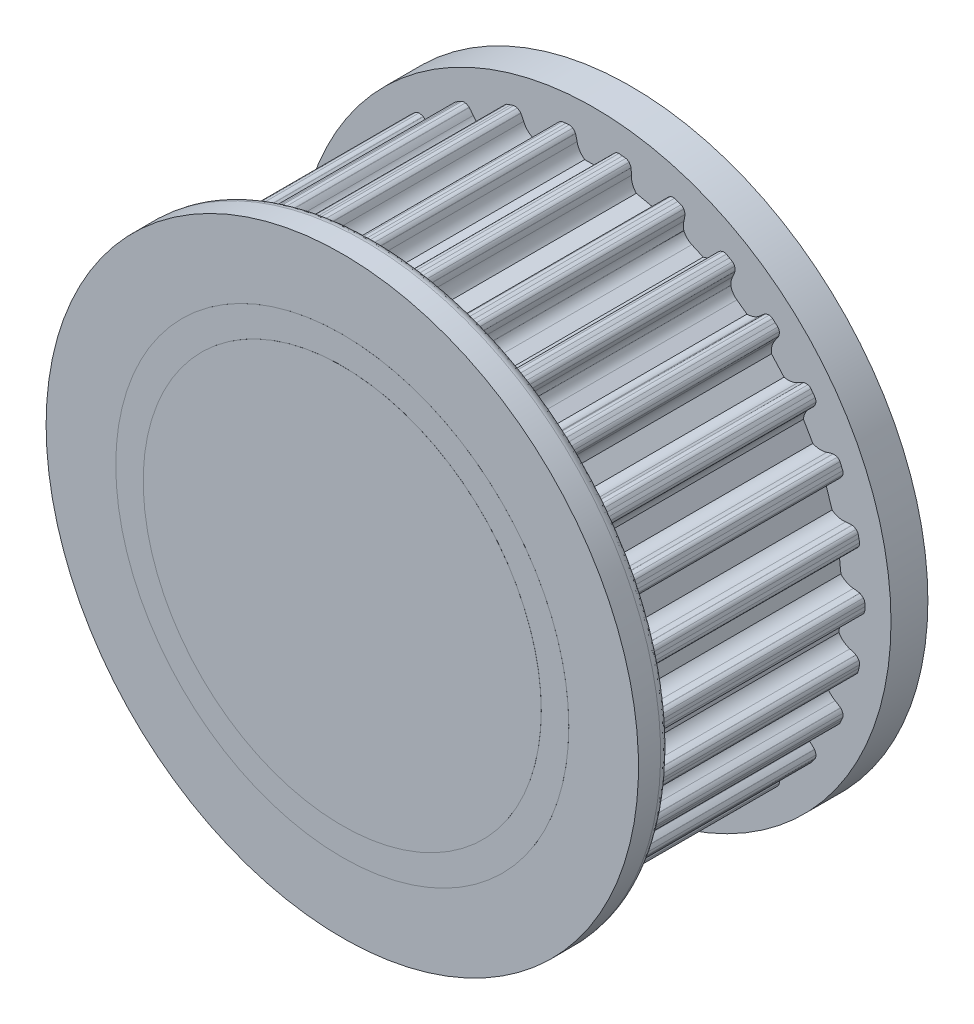
SolidWorks part; units mm, degrees
ref_plane "Front Plane" through (0, 0, 0) normal (0, 0, 1) x (1, 0, 0)
ref_plane "Top Plane" through (0, 0, 0) normal (0, 1, 0) x (1, 0, 0)
ref_plane "Right Plane" through (0, 0, 0) normal (1, 0, 0) x (0, 0, -1)
sketch "Sketch1" plane through (0, 0, 0) normal (0, 1, 0) x (1, 0, 0)
  line L0 (23.3317, 12.425) -> (0, 12.425)
  line L1 (0, 12.425) -> (0, 9.25)
  line L2 (0, 9.25) -> (23.3, 9.25)
  line L3 (23.3, 9.25) -> (25.5635, 9.25)
  line L4 (25.5635, 9.25) -> (25.5635, 12.425)
  line L5 (25.5635, 12.425) -> (23.3317, 12.425)
  line L6 (0, 11) -> (0, 9.25) construction
revolve "Revolve1" add sketch "Sketch1" angle 360 about L6 reverse direction yes
sketch "Sketch2" plane through (0, 0, -9.25) normal (0, 0, 1) x (1, 0, 0)
  line L0 (-22.221, 5.5321) -> (-22.1985, 5.5355)
  line L1 (-20.4892, 5.807) -> (-19.9894, 7.3453)
  line L2 (-21.2127, 8.5696) -> (-21.2288, 8.5856)
  line L3 (-20.5852, 10.0312) -> (-20.5625, 10.0299)
  line L4 (-18.8341, 9.9401) -> (-18.0254, 11.3408)
  line L5 (-18.9674, 12.7927) -> (-18.9799, 12.8117)
  line L6 (-18.0497, 14.0919) -> (-18.0278, 14.0859)
  line L7 (-16.3559, 13.6387) -> (-15.2736, 14.8406)
  line L8 (-15.8932, 16.4567) -> (-15.9015, 16.4779)
  line L9 (-14.7254, 17.5368) -> (-14.7053, 17.5263)
  line L10 (-13.1628, 16.7412) -> (-11.8543, 17.6919)
  line L11 (-12.1243, 19.4015) -> (-12.128, 19.4239)
  line L12 (-10.7575, 20.2151) -> (-10.74, 20.2007)
  line L13 (-9.3945, 19.1121) -> (-7.9169, 19.7699)
  line L14 (-7.8256, 21.4983) -> (-7.8246, 21.521)
  line L15 (-6.3195, 22.01) -> (-6.3053, 21.9922)
  line L16 (-5.2156, 20.6476) -> (-3.6335, 20.9839)
  line L17 (-3.1848, 22.6555) -> (-3.1791, 22.6775)
  line L18 (-1.6053, 22.8429) -> (-1.5951, 22.8226)
  line L19 (-0.8087, 21.2808) -> (0.8087, 21.2808)
  line L20 (1.5951, 22.8226) -> (1.6053, 22.8429)
  line L21 (3.1791, 22.6775) -> (3.1848, 22.6555)
  line L22 (3.6335, 20.9839) -> (5.2156, 20.6476)
  line L23 (6.3053, 21.9922) -> (6.3195, 22.01)
  line L24 (7.8246, 21.521) -> (7.8256, 21.4983)
  line L25 (7.7272, 20.2583) -> (7.9401, 19.7596)
  line L26 (7.9401, 19.7596) -> (9.3945, 19.1121)
  line L27 (10.74, 20.2007) -> (10.7575, 20.2151)
  line L28 (12.128, 19.4239) -> (12.1243, 19.4015)
  line L29 (11.7703, 18.209) -> (11.8749, 17.677)
  line L30 (11.8749, 17.677) -> (13.1628, 16.7412)
  line L31 (14.7053, 17.5263) -> (14.7254, 17.5368)
  line L32 (15.9015, 16.4779) -> (15.8932, 16.4567)
  line L33 (15.2736, 14.8406) -> (16.3559, 13.6387)
  line L34 (18.0278, 14.0859) -> (18.0497, 14.0919)
  line L35 (18.9799, 12.8117) -> (18.9674, 12.7927)
  line L36 (18.0254, 11.3408) -> (18.8341, 9.9401)
  line L37 (20.5625, 10.0299) -> (20.5852, 10.0312)
  line L38 (21.2288, 8.5856) -> (21.2127, 8.5696)
  line L39 (19.9894, 7.3453) -> (20.4892, 5.807)
  line L40 (22.1985, 5.5355) -> (22.221, 5.5321)
  line L41 (22.55, 3.9842) -> (22.5308, 3.972)
  line L42 (21.0797, 3.0287) -> (21.2488, 1.4202)
  line L43 (22.8643, 0.7992) -> (22.8856, 0.7912)
  line L44 (22.8856, -0.7912) -> (22.8643, -0.7992)
  line L45 (21.2488, -1.4202) -> (21.0797, -3.0287)
  line L46 (22.5308, -3.972) -> (22.55, -3.9842)
  line L47 (22.221, -5.5321) -> (22.1985, -5.5355)
  line L48 (20.4892, -5.807) -> (19.9894, -7.3453)
  line L49 (21.2127, -8.5696) -> (21.2288, -8.5856)
  line L50 (20.5852, -10.0312) -> (20.5625, -10.0299)
  line L51 (18.8341, -9.9401) -> (18.0254, -11.3408)
  line L52 (18.9674, -12.7927) -> (18.9799, -12.8117)
  line L53 (18.0497, -14.0919) -> (18.0278, -14.0859)
  line L54 (16.3559, -13.6387) -> (15.2736, -14.8406)
  line L55 (15.8932, -16.4567) -> (15.9015, -16.4779)
  line L56 (14.7254, -17.5368) -> (14.7053, -17.5263)
  line L57 (13.1628, -16.7412) -> (11.8749, -17.677)
  line L58 (11.8749, -17.677) -> (11.7703, -18.209)
  line L59 (12.1243, -19.4015) -> (12.128, -19.4239)
  line L60 (10.7575, -20.2151) -> (10.74, -20.2007)
  line L61 (9.3945, -19.1121) -> (7.9401, -19.7596)
  line L62 (7.9401, -19.7596) -> (7.7272, -20.2583)
  line L63 (7.8256, -21.4983) -> (7.8246, -21.521)
  line L64 (6.3195, -22.01) -> (6.3053, -21.9922)
  line L65 (5.2156, -20.6476) -> (3.6335, -20.9839)
  line L66 (3.1848, -22.6555) -> (3.1791, -22.6775)
  line L67 (1.6053, -22.8429) -> (1.5951, -22.8226)
  line L68 (0.8087, -21.2808) -> (-0.8087, -21.2808)
  line L69 (-1.5951, -22.8226) -> (-1.6053, -22.8429)
  line L70 (-3.1791, -22.6775) -> (-3.1848, -22.6555)
  line L71 (-3.6335, -20.9839) -> (-5.2156, -20.6476)
  line L72 (-6.3053, -21.9922) -> (-6.3195, -22.01)
  line L73 (-7.8246, -21.521) -> (-7.8256, -21.4983)
  line L74 (-7.9169, -19.7699) -> (-9.3945, -19.1121)
  line L75 (-10.74, -20.2007) -> (-10.7575, -20.2151)
  line L76 (-12.128, -19.4239) -> (-12.1243, -19.4015)
  line L77 (-11.8543, -17.6919) -> (-13.1628, -16.7412)
  line L78 (-14.7053, -17.5263) -> (-14.7254, -17.5368)
  line L79 (-15.9015, -16.4779) -> (-15.8932, -16.4567)
  line L80 (-15.2736, -14.8406) -> (-16.3559, -13.6387)
  line L81 (-18.0278, -14.0859) -> (-18.0497, -14.0919)
  line L82 (-18.9799, -12.8117) -> (-18.9674, -12.7927)
  line L83 (-18.0254, -11.3408) -> (-18.8341, -9.9401)
  line L84 (-20.5625, -10.0299) -> (-20.5852, -10.0312)
  line L85 (-21.2288, -8.5856) -> (-21.2127, -8.5696)
  line L86 (-19.9894, -7.3453) -> (-20.4892, -5.807)
  line L87 (-22.1985, -5.5355) -> (-22.221, -5.5321)
  line L88 (-22.55, -3.9842) -> (-22.5308, -3.972)
  line L89 (-21.0797, -3.0287) -> (-21.2488, -1.4202)
  line L90 (-22.8643, -0.7992) -> (-22.8856, -0.7912)
  line L91 (-22.8856, 0.7912) -> (-22.8643, 0.7992)
  line L92 (-21.2488, 1.4202) -> (-21.0797, 3.0287)
  line L93 (-22.5308, 3.972) -> (-22.55, 3.9842)
  arc A0 (-22.8557, 4.5501) -> (-22.7941, 4.845) centre (-18.765, 3.8489) cw
  arc A1 (-22.7941, 4.845) -> (-22.7305, 5.1395) centre (-18.7082, 4.1162) cw
  arc A2 (-22.7305, 5.1395) -> (-22.5533, 5.3971) centre (-22.2151, 4.9748) cw
  arc A3 (-22.5533, 5.3971) -> (-22.221, 5.5321) centre (-22.0388, 4.6076) cw
  arc A4 (-22.1985, 5.5355) -> (-21.6552, 5.4979) centre (-22.2209, 1.2735) cw
  arc A5 (-21.6552, 5.4979) -> (-20.4892, 5.807) centre (-21.4632, 7.1274) ccw
  arc A6 (-19.9894, 7.3453) -> (-20.751, 8.2807) centre (-21.5535, 6.8495) ccw
  arc A7 (-20.751, 8.2807) -> (-21.2127, 8.5696) centre (-18.7256, 12.0308) cw
  arc A8 (-21.2288, 8.5856) -> (-21.4183, 8.8902) centre (-20.538, 9.2265) cw
  arc A9 (-21.4183, 8.8902) -> (-21.4102, 9.2027) centre (-20.8965, 9.0331) cw
  arc A10 (-21.4102, 9.2027) -> (-21.2886, 9.4783) centre (-17.5547, 7.6663) cw
  arc A11 (-21.2886, 9.4783) -> (-21.1652, 9.7531) centre (-17.4436, 7.916) cw
  arc A12 (-21.1652, 9.7531) -> (-20.9383, 9.9682) centre (-20.6954, 9.4848) cw
  arc A13 (-20.9383, 9.9682) -> (-20.5852, 10.0312) centre (-20.5992, 9.089) cw
  arc A14 (-20.5625, 10.0299) -> (-20.0389, 9.8801) centre (-21.4705, 5.8657) cw
  arc A15 (-20.0389, 9.8801) -> (-18.8341, 9.9401) centre (-19.5123, 11.4341) ccw
  arc A16 (-18.0254, 11.3408) -> (-18.5759, 12.4142) centre (-19.6584, 11.1811) ccw
  arc A17 (-18.5759, 12.4142) -> (-18.9674, 12.7927) centre (-15.8151, 15.6612) cw
  arc A18 (-18.9799, 12.8117) -> (-19.1019, 13.149) centre (-18.1709, 13.295) cw
  arc A19 (-19.1019, 13.149) -> (-19.029, 13.453) centre (-18.5618, 13.1803) cw
  arc A20 (-19.029, 13.453) -> (-18.8528, 13.6973) centre (-15.5772, 11.1486) cw
  arc A21 (-18.8528, 13.6973) -> (-18.6749, 13.9405) centre (-15.4166, 11.3697) cw
  arc A22 (-18.6749, 13.9405) -> (-18.4083, 14.1037) centre (-18.2711, 13.5804) cw
  arc A23 (-18.4083, 14.1037) -> (-18.0497, 14.0919) centre (-18.2594, 13.1732) cw
  arc A24 (-18.0278, 14.0859) -> (-17.5468, 13.8305) centre (-19.7818, 10.2014) cw
  arc A25 (-17.5468, 13.8305) -> (-16.3559, 13.6387) centre (-16.7086, 15.2411) ccw
  arc A26 (-15.2736, 14.8406) -> (-15.5889, 16.005) centre (-16.9042, 15.024) ccw
  arc A27 (-15.5889, 16.005) -> (-15.8932, 16.4567) centre (-12.2133, 18.6071) cw
  arc A28 (-15.9015, 16.4779) -> (-15.9507, 16.8332) centre (-15.0097, 16.7824) cw
  arc A29 (-15.9507, 16.8332) -> (-15.8162, 17.1154) centre (-15.4158, 16.7515) cw
  arc A30 (-15.8162, 17.1154) -> (-15.593, 17.3177) centre (-12.9189, 14.1437) cw
  arc A31 (-15.593, 17.3177) -> (-15.3684, 17.5186) centre (-12.7158, 14.3265) cw
  arc A32 (-15.3684, 17.5186) -> (-15.0737, 17.6228) centre (-15.0483, 17.0824) cw
  arc A33 (-15.0737, 17.6228) -> (-14.7254, 17.5368) centre (-15.1215, 16.6817) cw
  arc A34 (-14.7053, 17.5263) -> (-14.2879, 17.1765) centre (-17.2285, 14.0914) cw
  arc A35 (-14.2879, 17.1765) -> (-13.1628, 16.7412) centre (-13.1747, 18.382) ccw
  arc A36 (-11.8543, 17.6919) -> (-11.9206, 18.8964) centre (-13.4111, 18.2102) ccw
  arc A37 (-11.9206, 18.8964) -> (-12.1243, 19.4015) centre (-8.0778, 20.7398) cw
  arc A38 (-12.128, 19.4239) -> (-12.1023, 19.7817) centre (-11.1924, 19.5363) cw
  arc A39 (-12.1023, 19.7817) -> (-11.9121, 20.0298) centre (-11.5961, 19.5906) cw
  arc A40 (-11.9121, 20.0298) -> (-11.6517, 20.1813) centre (-9.6959, 16.5206) cw
  arc A41 (-11.6517, 20.1813) -> (-11.3902, 20.331) centre (-9.4593, 16.6572) cw
  arc A42 (-11.3902, 20.331) -> (-11.0803, 20.3717) centre (-11.1678, 19.8378) cw
  arc A43 (-11.0803, 20.3717) -> (-10.7575, 20.2151) centre (-11.3228, 19.4611) cw
  arc A44 (-10.74, 20.2007) -> (-10.4045, 19.7718) centre (-13.9223, 17.3655) cw
  arc A45 (-10.4045, 19.7718) -> (-9.3945, 19.1121) centre (-9.065, 20.7195) ccw
  arc A46 (-7.9169, 19.7699) -> (-7.7313, 20.9619) centre (-9.3319, 20.6006) ccw
  arc A47 (-7.7313, 20.9619) -> (-7.8256, 21.4983) centre (-3.5892, 21.966) cw
  arc A48 (-7.8246, 21.521) -> (-7.725, 21.8656) centre (-6.886, 21.4365) cw
  arc A49 (-7.725, 21.8656) -> (-7.4873, 22.0687) centre (-7.2696, 21.5734) cw
  arc A50 (-7.4873, 22.0687) -> (-7.2011, 22.1628) centre (-6.0492, 18.1755) cw
  arc A51 (-7.2011, 22.1628) -> (-6.9143, 22.2549) centre (-5.7893, 18.2599) cw
  arc A52 (-6.9143, 22.2549) -> (-6.6026, 22.2303) centre (-6.7993, 21.7262) cw
  arc A53 (-6.6026, 22.2303) -> (-6.3195, 22.01) centre (-7.0291, 21.39) cw
  arc A54 (-6.3053, 21.9922) -> (-6.0663, 21.5029) centre (-10.0076, 19.8806) cw
  arc A55 (-6.0663, 21.5029) -> (-5.2156, 20.6476) centre (-4.5591, 22.1514) ccw
  arc A56 (-3.6335, 20.9839) -> (-3.2042, 22.1113) centre (-4.8449, 22.0907) ccw
  arc A57 (-3.2042, 22.1113) -> (-3.1848, 22.6555) centre (1.0562, 22.2323) cw
  arc A58 (-3.1791, 22.6775) -> (-3.0101, 22.9939) centre (-2.2786, 22.3997) cw
  arc A59 (-3.0101, 22.9939) -> (-2.7354, 23.1432) centre (-2.6254, 22.6134) cw
  arc A60 (-2.7354, 23.1432) -> (-2.4359, 23.1757) centre (-2.1382, 19.036) cw
  arc A61 (-2.4359, 23.1757) -> (-2.1361, 23.2061) centre (-1.8664, 19.0646) cw
  arc A62 (-2.1361, 23.2061) -> (-1.8364, 23.1172) centre (-2.1336, 22.6651) cw
  arc A63 (-1.8364, 23.1172) -> (-1.6053, 22.8429) centre (-2.4283, 22.384) cw
  arc A64 (-1.5951, 22.8226) -> (-1.463, 22.2943) centre (-5.6555, 21.5268) cw
  arc A65 (-1.463, 22.2943) -> (-0.8087, 21.2808) centre (0.1461, 22.6152) ccw
  arc A66 (0.8087, 21.2808) -> (1.463, 22.2943) centre (-0.1461, 22.6152) ccw
  arc A67 (1.463, 22.2943) -> (1.5951, 22.8226) centre (5.6555, 21.5268) cw
  arc A68 (1.6053, 22.8429) -> (1.8364, 23.1172) centre (2.4283, 22.384) cw
  arc A69 (1.8364, 23.1172) -> (2.1361, 23.2061) centre (2.1336, 22.6651) cw
  arc A70 (2.1361, 23.2061) -> (2.4359, 23.1757) centre (1.8664, 19.0646) cw
  arc A71 (2.4359, 23.1757) -> (2.7354, 23.1432) centre (2.1382, 19.036) cw
  arc A72 (2.7354, 23.1432) -> (3.0101, 22.9939) centre (2.6254, 22.6134) cw
  arc A73 (3.0101, 22.9939) -> (3.1791, 22.6775) centre (2.2786, 22.3997) cw
  arc A74 (3.1848, 22.6555) -> (3.2042, 22.1113) centre (-1.0562, 22.2323) cw
  arc A75 (3.2042, 22.1113) -> (3.6335, 20.9839) centre (4.8449, 22.0907) ccw
  arc A76 (5.2156, 20.6476) -> (6.0663, 21.5029) centre (4.5591, 22.1514) ccw
  arc A77 (6.0663, 21.5029) -> (6.3053, 21.9922) centre (10.0076, 19.8806) cw
  arc A78 (6.3195, 22.01) -> (6.6026, 22.2303) centre (7.0291, 21.39) cw
  arc A79 (6.6026, 22.2303) -> (6.9143, 22.2549) centre (6.7993, 21.7262) cw
  arc A80 (6.9143, 22.2549) -> (7.2011, 22.1628) centre (5.7893, 18.2599) cw
  arc A81 (7.2011, 22.1628) -> (7.4873, 22.0687) centre (6.0492, 18.1755) cw
  arc A82 (7.4873, 22.0687) -> (7.725, 21.8656) centre (7.2696, 21.5734) cw
  arc A83 (7.725, 21.8656) -> (7.8246, 21.521) centre (6.886, 21.4365) cw
  arc A84 (7.8256, 21.4983) -> (7.7313, 20.9619) centre (3.5892, 21.966) cw
  arc A85 (7.7313, 20.9619) -> (7.7272, 20.2583) centre (9.3319, 20.6006) ccw
  arc A86 (9.3945, 19.1121) -> (10.4045, 19.7718) centre (9.065, 20.7195) ccw
  arc A87 (10.4045, 19.7718) -> (10.74, 20.2007) centre (13.9223, 17.3655) cw
  arc A88 (10.7575, 20.2151) -> (11.0803, 20.3717) centre (11.3228, 19.4611) cw
  arc A89 (11.0803, 20.3717) -> (11.3902, 20.331) centre (11.1678, 19.8378) cw
  arc A90 (11.3902, 20.331) -> (11.6517, 20.1813) centre (9.4593, 16.6572) cw
  arc A91 (11.6517, 20.1813) -> (11.9121, 20.0298) centre (9.6959, 16.5206) cw
  arc A92 (11.9121, 20.0298) -> (12.1023, 19.7817) centre (11.5961, 19.5906) cw
  arc A93 (12.1023, 19.7817) -> (12.128, 19.4239) centre (11.1924, 19.5363) cw
  arc A94 (12.1243, 19.4015) -> (11.9206, 18.8964) centre (8.0778, 20.7398) cw
  arc A95 (11.9206, 18.8964) -> (11.7703, 18.209) centre (13.4111, 18.2102) ccw
  arc A96 (13.1628, 16.7412) -> (14.2879, 17.1765) centre (13.1747, 18.382) ccw
  arc A97 (14.2879, 17.1765) -> (14.7053, 17.5263) centre (17.2285, 14.0914) cw
  arc A98 (14.7254, 17.5368) -> (15.0737, 17.6228) centre (15.1215, 16.6817) cw
  arc A99 (15.0737, 17.6228) -> (15.3684, 17.5186) centre (15.0483, 17.0824) cw
  arc A100 (15.3684, 17.5186) -> (15.593, 17.3177) centre (12.7158, 14.3265) cw
  arc A101 (15.593, 17.3177) -> (15.8162, 17.1154) centre (12.9189, 14.1437) cw
  arc A102 (15.8162, 17.1154) -> (15.9507, 16.8332) centre (15.4158, 16.7515) cw
  arc A103 (15.9507, 16.8332) -> (15.9015, 16.4779) centre (15.0097, 16.7824) cw
  arc A104 (15.8932, 16.4567) -> (15.5889, 16.005) centre (12.2133, 18.6071) cw
  arc A105 (15.5889, 16.005) -> (15.2736, 14.8406) centre (16.9042, 15.024) ccw
  arc A106 (16.3559, 13.6387) -> (17.5468, 13.8305) centre (16.7086, 15.2411) ccw
  arc A107 (17.5468, 13.8305) -> (18.0278, 14.0859) centre (19.7818, 10.2014) cw
  arc A108 (18.0497, 14.0919) -> (18.4083, 14.1037) centre (18.2594, 13.1732) cw
  arc A109 (18.4083, 14.1037) -> (18.6749, 13.9405) centre (18.2711, 13.5804) cw
  arc A110 (18.6749, 13.9405) -> (18.8528, 13.6973) centre (15.4166, 11.3697) cw
  arc A111 (18.8528, 13.6973) -> (19.029, 13.453) centre (15.5772, 11.1486) cw
  arc A112 (19.029, 13.453) -> (19.1019, 13.149) centre (18.5618, 13.1803) cw
  arc A113 (19.1019, 13.149) -> (18.9799, 12.8117) centre (18.1709, 13.295) cw
  arc A114 (18.9674, 12.7927) -> (18.5759, 12.4142) centre (15.8151, 15.6612) cw
  arc A115 (18.5759, 12.4142) -> (18.0254, 11.3408) centre (19.6584, 11.1811) ccw
  arc A116 (18.8341, 9.9401) -> (20.0389, 9.8801) centre (19.5123, 11.4341) ccw
  arc A117 (20.0389, 9.8801) -> (20.5625, 10.0299) centre (21.4705, 5.8657) cw
  arc A118 (20.5852, 10.0312) -> (20.9383, 9.9682) centre (20.5992, 9.089) cw
  arc A119 (20.9383, 9.9682) -> (21.1652, 9.7531) centre (20.6954, 9.4848) cw
  arc A120 (21.1652, 9.7531) -> (21.2886, 9.4783) centre (17.4436, 7.916) cw
  arc A121 (21.2886, 9.4783) -> (21.4102, 9.2027) centre (17.5547, 7.6663) cw
  arc A122 (21.4102, 9.2027) -> (21.4183, 8.8902) centre (20.8965, 9.0331) cw
  arc A123 (21.4183, 8.8902) -> (21.2288, 8.5856) centre (20.538, 9.2265) cw
  arc A124 (21.2127, 8.5696) -> (20.751, 8.2807) centre (18.7256, 12.0308) cw
  arc A125 (20.751, 8.2807) -> (19.9894, 7.3453) centre (21.5535, 6.8495) ccw
  arc A126 (20.4892, 5.807) -> (21.6552, 5.4979) centre (21.4632, 7.1274) ccw
  arc A127 (21.6552, 5.4979) -> (22.1985, 5.5355) centre (22.2209, 1.2735) cw
  arc A128 (22.221, 5.5321) -> (22.5533, 5.3971) centre (22.0388, 4.6076) cw
  arc A129 (22.5533, 5.3971) -> (22.7305, 5.1395) centre (22.2151, 4.9748) cw
  arc A130 (22.7305, 5.1395) -> (22.7941, 4.845) centre (18.7082, 4.1162) cw
  arc A131 (22.7941, 4.845) -> (22.8557, 4.5501) centre (18.765, 3.8489) cw
  arc A132 (22.8557, 4.5501) -> (22.7986, 4.2428) centre (22.3179, 4.491) cw
  arc A133 (22.7986, 4.2428) -> (22.55, 3.9842) centre (22.0075, 4.7548) cw
  arc A134 (22.5308, 3.972) -> (22.0192, 3.7854) centre (20.8178, 7.8746) cw
  arc A135 (22.0192, 3.7854) -> (21.0797, 3.0287) centre (22.5066, 2.2186) ccw
  arc A136 (21.2488, 1.4202) -> (22.3251, 0.8754) centre (22.4761, 2.5092) ccw
  arc A137 (22.3251, 0.8754) -> (22.8643, 0.7992) centre (22.0001, -3.3743) cw
  arc A138 (22.8856, 0.7912) -> (23.1826, 0.59) centre (22.5152, -0.0752) cw
  arc A139 (23.1826, 0.59) -> (23.3023, 0.3013) centre (22.764, 0.2473) cw
  arc A140 (23.3023, 0.3013) -> (23.3033, 0) centre (19.1552, 0.1366) cw
  arc A141 (23.3033, 0) -> (23.3023, -0.3013) centre (19.1552, -0.1366) cw
  arc A142 (23.3023, -0.3013) -> (23.1826, -0.59) centre (22.764, -0.2473) cw
  arc A143 (23.1826, -0.59) -> (22.8856, -0.7912) centre (22.5152, 0.0752) cw
  arc A144 (22.8643, -0.7992) -> (22.3251, -0.8754) centre (22.0001, 3.3743) cw
  arc A145 (22.3251, -0.8754) -> (21.2488, -1.4202) centre (22.4761, -2.5092) ccw
  arc A146 (21.0797, -3.0287) -> (22.0192, -3.7854) centre (22.5066, -2.2186) ccw
  arc A147 (22.0192, -3.7854) -> (22.5308, -3.972) centre (20.8178, -7.8746) cw
  arc A148 (22.55, -3.9842) -> (22.7986, -4.2428) centre (22.0075, -4.7548) cw
  arc A149 (22.7986, -4.2428) -> (22.8557, -4.5501) centre (22.3179, -4.491) cw
  arc A150 (22.8557, -4.5501) -> (22.7941, -4.845) centre (18.765, -3.8489) cw
  arc A151 (22.7941, -4.845) -> (22.7305, -5.1395) centre (18.7082, -4.1162) cw
  arc A152 (22.7305, -5.1395) -> (22.5533, -5.3971) centre (22.2151, -4.9748) cw
  arc A153 (22.5533, -5.3971) -> (22.221, -5.5321) centre (22.0388, -4.6076) cw
  arc A154 (22.1985, -5.5355) -> (21.6552, -5.4979) centre (22.2209, -1.2735) cw
  arc A155 (21.6552, -5.4979) -> (20.4892, -5.807) centre (21.4632, -7.1274) ccw
  arc A156 (19.9894, -7.3453) -> (20.751, -8.2807) centre (21.5535, -6.8495) ccw
  arc A157 (20.751, -8.2807) -> (21.2127, -8.5696) centre (18.7256, -12.0308) cw
  arc A158 (21.2288, -8.5856) -> (21.4183, -8.8902) centre (20.538, -9.2265) cw
  arc A159 (21.4183, -8.8902) -> (21.4102, -9.2027) centre (20.8965, -9.0331) cw
  arc A160 (21.4102, -9.2027) -> (21.2886, -9.4783) centre (17.5547, -7.6663) cw
  arc A161 (21.2886, -9.4783) -> (21.1652, -9.7531) centre (17.4436, -7.916) cw
  arc A162 (21.1652, -9.7531) -> (20.9383, -9.9682) centre (20.6954, -9.4848) cw
  arc A163 (20.9383, -9.9682) -> (20.5852, -10.0312) centre (20.5992, -9.089) cw
  arc A164 (20.5625, -10.0299) -> (20.0389, -9.8801) centre (21.4705, -5.8657) cw
  arc A165 (20.0389, -9.8801) -> (18.8341, -9.9401) centre (19.5123, -11.4341) ccw
  arc A166 (18.0254, -11.3408) -> (18.5759, -12.4142) centre (19.6584, -11.1811) ccw
  arc A167 (18.5759, -12.4142) -> (18.9674, -12.7927) centre (15.8151, -15.6612) cw
  arc A168 (18.9799, -12.8117) -> (19.1019, -13.149) centre (18.1709, -13.295) cw
  arc A169 (19.1019, -13.149) -> (19.029, -13.453) centre (18.5618, -13.1803) cw
  arc A170 (19.029, -13.453) -> (18.8528, -13.6973) centre (15.5772, -11.1486) cw
  arc A171 (18.8528, -13.6973) -> (18.6749, -13.9405) centre (15.4166, -11.3697) cw
  arc A172 (18.6749, -13.9405) -> (18.4083, -14.1037) centre (18.2711, -13.5804) cw
  arc A173 (18.4083, -14.1037) -> (18.0497, -14.0919) centre (18.2594, -13.1732) cw
  arc A174 (18.0278, -14.0859) -> (17.5468, -13.8305) centre (19.7818, -10.2014) cw
  arc A175 (17.5468, -13.8305) -> (16.3559, -13.6387) centre (16.7086, -15.2411) ccw
  arc A176 (15.2736, -14.8406) -> (15.5889, -16.005) centre (16.9042, -15.024) ccw
  arc A177 (15.5889, -16.005) -> (15.8932, -16.4567) centre (12.2133, -18.6071) cw
  arc A178 (15.9015, -16.4779) -> (15.9507, -16.8332) centre (15.0097, -16.7824) cw
  arc A179 (15.9507, -16.8332) -> (15.8162, -17.1154) centre (15.4158, -16.7515) cw
  arc A180 (15.8162, -17.1154) -> (15.593, -17.3177) centre (12.9189, -14.1437) cw
  arc A181 (15.593, -17.3177) -> (15.3684, -17.5186) centre (12.7158, -14.3265) cw
  arc A182 (15.3684, -17.5186) -> (15.0737, -17.6228) centre (15.0483, -17.0824) cw
  arc A183 (15.0737, -17.6228) -> (14.7254, -17.5368) centre (15.1215, -16.6817) cw
  arc A184 (14.7053, -17.5263) -> (14.2879, -17.1765) centre (17.2285, -14.0914) cw
  arc A185 (14.2879, -17.1765) -> (13.1628, -16.7412) centre (13.1747, -18.382) ccw
  arc A186 (11.7703, -18.209) -> (11.9206, -18.8964) centre (13.4111, -18.2102) ccw
  arc A187 (11.9206, -18.8964) -> (12.1243, -19.4015) centre (8.0778, -20.7398) cw
  arc A188 (12.128, -19.4239) -> (12.1023, -19.7817) centre (11.1924, -19.5363) cw
  arc A189 (12.1023, -19.7817) -> (11.9121, -20.0298) centre (11.5961, -19.5906) cw
  arc A190 (11.9121, -20.0298) -> (11.6517, -20.1813) centre (9.6959, -16.5206) cw
  arc A191 (11.6517, -20.1813) -> (11.3902, -20.331) centre (9.4593, -16.6572) cw
  arc A192 (11.3902, -20.331) -> (11.0803, -20.3717) centre (11.1678, -19.8378) cw
  arc A193 (11.0803, -20.3717) -> (10.7575, -20.2151) centre (11.3228, -19.4611) cw
  arc A194 (10.74, -20.2007) -> (10.4045, -19.7718) centre (13.9223, -17.3655) cw
  arc A195 (10.4045, -19.7718) -> (9.3945, -19.1121) centre (9.065, -20.7195) ccw
  arc A196 (7.7272, -20.2583) -> (7.7313, -20.9619) centre (9.3319, -20.6006) ccw
  arc A197 (7.7313, -20.9619) -> (7.8256, -21.4983) centre (3.5892, -21.966) cw
  arc A198 (7.8246, -21.521) -> (7.725, -21.8656) centre (6.886, -21.4365) cw
  arc A199 (7.725, -21.8656) -> (7.4873, -22.0687) centre (7.2696, -21.5734) cw
  arc A200 (7.4873, -22.0687) -> (7.2011, -22.1628) centre (6.0492, -18.1755) cw
  arc A201 (7.2011, -22.1628) -> (6.9143, -22.2549) centre (5.7893, -18.2599) cw
  arc A202 (6.9143, -22.2549) -> (6.6026, -22.2303) centre (6.7993, -21.7262) cw
  arc A203 (6.6026, -22.2303) -> (6.3195, -22.01) centre (7.0291, -21.39) cw
  arc A204 (6.3053, -21.9922) -> (6.0663, -21.5029) centre (10.0076, -19.8806) cw
  arc A205 (6.0663, -21.5029) -> (5.2156, -20.6476) centre (4.5591, -22.1514) ccw
  arc A206 (3.6335, -20.9839) -> (3.2042, -22.1113) centre (4.8449, -22.0907) ccw
  arc A207 (3.2042, -22.1113) -> (3.1848, -22.6555) centre (-1.0562, -22.2323) cw
  arc A208 (3.1791, -22.6775) -> (3.0101, -22.9939) centre (2.2786, -22.3997) cw
  arc A209 (3.0101, -22.9939) -> (2.7354, -23.1432) centre (2.6254, -22.6134) cw
  arc A210 (2.7354, -23.1432) -> (2.4359, -23.1757) centre (2.1382, -19.036) cw
  arc A211 (2.4359, -23.1757) -> (2.1361, -23.2061) centre (1.8664, -19.0646) cw
  arc A212 (2.1361, -23.2061) -> (1.8364, -23.1172) centre (2.1336, -22.6651) cw
  arc A213 (1.8364, -23.1172) -> (1.6053, -22.8429) centre (2.4283, -22.384) cw
  arc A214 (1.5951, -22.8226) -> (1.463, -22.2943) centre (5.6555, -21.5268) cw
  arc A215 (1.463, -22.2943) -> (0.8087, -21.2808) centre (-0.1461, -22.6152) ccw
  arc A216 (-0.8087, -21.2808) -> (-1.463, -22.2943) centre (0.1461, -22.6152) ccw
  arc A217 (-1.463, -22.2943) -> (-1.5951, -22.8226) centre (-5.6555, -21.5268) cw
  arc A218 (-1.6053, -22.8429) -> (-1.8364, -23.1172) centre (-2.4283, -22.384) cw
  arc A219 (-1.8364, -23.1172) -> (-2.1361, -23.2061) centre (-2.1336, -22.6651) cw
  arc A220 (-2.1361, -23.2061) -> (-2.4359, -23.1757) centre (-1.8664, -19.0646) cw
  arc A221 (-2.4359, -23.1757) -> (-2.7354, -23.1432) centre (-2.1382, -19.036) cw
  arc A222 (-2.7354, -23.1432) -> (-3.0101, -22.9939) centre (-2.6254, -22.6134) cw
  arc A223 (-3.0101, -22.9939) -> (-3.1791, -22.6775) centre (-2.2786, -22.3997) cw
  arc A224 (-3.1848, -22.6555) -> (-3.2042, -22.1113) centre (1.0562, -22.2323) cw
  arc A225 (-3.2042, -22.1113) -> (-3.6335, -20.9839) centre (-4.8449, -22.0907) ccw
  arc A226 (-5.2156, -20.6476) -> (-6.0663, -21.5029) centre (-4.5591, -22.1514) ccw
  arc A227 (-6.0663, -21.5029) -> (-6.3053, -21.9922) centre (-10.0076, -19.8806) cw
  arc A228 (-6.3195, -22.01) -> (-6.6026, -22.2303) centre (-7.0291, -21.39) cw
  arc A229 (-6.6026, -22.2303) -> (-6.9143, -22.2549) centre (-6.7993, -21.7262) cw
  arc A230 (-6.9143, -22.2549) -> (-7.2011, -22.1628) centre (-5.7893, -18.2599) cw
  arc A231 (-7.2011, -22.1628) -> (-7.4873, -22.0687) centre (-6.0492, -18.1755) cw
  arc A232 (-7.4873, -22.0687) -> (-7.725, -21.8656) centre (-7.2696, -21.5734) cw
  arc A233 (-7.725, -21.8656) -> (-7.8246, -21.521) centre (-6.886, -21.4365) cw
  arc A234 (-7.8256, -21.4983) -> (-7.7313, -20.9619) centre (-3.5892, -21.966) cw
  arc A235 (-7.7313, -20.9619) -> (-7.9169, -19.7699) centre (-9.3319, -20.6006) ccw
  arc A236 (-9.3945, -19.1121) -> (-10.4045, -19.7718) centre (-9.065, -20.7195) ccw
  arc A237 (-10.4045, -19.7718) -> (-10.74, -20.2007) centre (-13.9223, -17.3655) cw
  arc A238 (-10.7575, -20.2151) -> (-11.0803, -20.3717) centre (-11.3228, -19.4611) cw
  arc A239 (-11.0803, -20.3717) -> (-11.3902, -20.331) centre (-11.1678, -19.8378) cw
  arc A240 (-11.3902, -20.331) -> (-11.6517, -20.1813) centre (-9.4593, -16.6572) cw
  arc A241 (-11.6517, -20.1813) -> (-11.9121, -20.0298) centre (-9.6959, -16.5206) cw
  arc A242 (-11.9121, -20.0298) -> (-12.1023, -19.7817) centre (-11.5961, -19.5906) cw
  arc A243 (-12.1023, -19.7817) -> (-12.128, -19.4239) centre (-11.1924, -19.5363) cw
  arc A244 (-12.1243, -19.4015) -> (-11.9206, -18.8964) centre (-8.0778, -20.7398) cw
  arc A245 (-11.9206, -18.8964) -> (-11.8543, -17.6919) centre (-13.4111, -18.2102) ccw
  arc A246 (-13.1628, -16.7412) -> (-14.2879, -17.1765) centre (-13.1747, -18.382) ccw
  arc A247 (-14.2879, -17.1765) -> (-14.7053, -17.5263) centre (-17.2285, -14.0914) cw
  arc A248 (-14.7254, -17.5368) -> (-15.0737, -17.6228) centre (-15.1215, -16.6817) cw
  arc A249 (-15.0737, -17.6228) -> (-15.3684, -17.5186) centre (-15.0483, -17.0824) cw
  arc A250 (-15.3684, -17.5186) -> (-15.593, -17.3177) centre (-12.7158, -14.3265) cw
  arc A251 (-15.593, -17.3177) -> (-15.8162, -17.1154) centre (-12.9189, -14.1437) cw
  arc A252 (-15.8162, -17.1154) -> (-15.9507, -16.8332) centre (-15.4158, -16.7515) cw
  arc A253 (-15.9507, -16.8332) -> (-15.9015, -16.4779) centre (-15.0097, -16.7824) cw
  arc A254 (-15.8932, -16.4567) -> (-15.5889, -16.005) centre (-12.2133, -18.6071) cw
  arc A255 (-15.5889, -16.005) -> (-15.2736, -14.8406) centre (-16.9042, -15.024) ccw
  arc A256 (-16.3559, -13.6387) -> (-17.5468, -13.8305) centre (-16.7086, -15.2411) ccw
  arc A257 (-17.5468, -13.8305) -> (-18.0278, -14.0859) centre (-19.7818, -10.2014) cw
  arc A258 (-18.0497, -14.0919) -> (-18.4083, -14.1037) centre (-18.2594, -13.1732) cw
  arc A259 (-18.4083, -14.1037) -> (-18.6749, -13.9405) centre (-18.2711, -13.5804) cw
  arc A260 (-18.6749, -13.9405) -> (-18.8528, -13.6973) centre (-15.4166, -11.3697) cw
  arc A261 (-18.8528, -13.6973) -> (-19.029, -13.453) centre (-15.5772, -11.1486) cw
  arc A262 (-19.029, -13.453) -> (-19.1019, -13.149) centre (-18.5618, -13.1803) cw
  arc A263 (-19.1019, -13.149) -> (-18.9799, -12.8117) centre (-18.1709, -13.295) cw
  arc A264 (-18.9674, -12.7927) -> (-18.5759, -12.4142) centre (-15.8151, -15.6612) cw
  arc A265 (-18.5759, -12.4142) -> (-18.0254, -11.3408) centre (-19.6584, -11.1811) ccw
  arc A266 (-18.8341, -9.9401) -> (-20.0389, -9.8801) centre (-19.5123, -11.4341) ccw
  arc A267 (-20.0389, -9.8801) -> (-20.5625, -10.0299) centre (-21.4705, -5.8657) cw
  arc A268 (-20.5852, -10.0312) -> (-20.9383, -9.9682) centre (-20.5992, -9.089) cw
  arc A269 (-20.9383, -9.9682) -> (-21.1652, -9.7531) centre (-20.6954, -9.4848) cw
  arc A270 (-21.1652, -9.7531) -> (-21.2886, -9.4783) centre (-17.4436, -7.916) cw
  arc A271 (-21.2886, -9.4783) -> (-21.4102, -9.2027) centre (-17.5547, -7.6663) cw
  arc A272 (-21.4102, -9.2027) -> (-21.4183, -8.8902) centre (-20.8965, -9.0331) cw
  arc A273 (-21.4183, -8.8902) -> (-21.2288, -8.5856) centre (-20.538, -9.2265) cw
  arc A274 (-21.2127, -8.5696) -> (-20.751, -8.2807) centre (-18.7256, -12.0308) cw
  arc A275 (-20.751, -8.2807) -> (-19.9894, -7.3453) centre (-21.5535, -6.8495) ccw
  arc A276 (-20.4892, -5.807) -> (-21.6552, -5.4979) centre (-21.4632, -7.1274) ccw
  arc A277 (-21.6552, -5.4979) -> (-22.1985, -5.5355) centre (-22.2209, -1.2735) cw
  arc A278 (-22.221, -5.5321) -> (-22.5533, -5.3971) centre (-22.0388, -4.6076) cw
  arc A279 (-22.5533, -5.3971) -> (-22.7305, -5.1395) centre (-22.2151, -4.9748) cw
  arc A280 (-22.7305, -5.1395) -> (-22.7941, -4.845) centre (-18.7082, -4.1162) cw
  arc A281 (-22.7941, -4.845) -> (-22.8557, -4.5501) centre (-18.765, -3.8489) cw
  arc A282 (-22.8557, -4.5501) -> (-22.7986, -4.2428) centre (-22.3179, -4.491) cw
  arc A283 (-22.7986, -4.2428) -> (-22.55, -3.9842) centre (-22.0075, -4.7548) cw
  arc A284 (-22.5308, -3.972) -> (-22.0192, -3.7854) centre (-20.8178, -7.8746) cw
  arc A285 (-22.0192, -3.7854) -> (-21.0797, -3.0287) centre (-22.5066, -2.2186) ccw
  arc A286 (-21.2488, -1.4202) -> (-22.3251, -0.8754) centre (-22.4761, -2.5092) ccw
  arc A287 (-22.3251, -0.8754) -> (-22.8643, -0.7992) centre (-22.0001, 3.3743) cw
  arc A288 (-22.8856, -0.7912) -> (-23.1826, -0.59) centre (-22.5152, 0.0752) cw
  arc A289 (-23.1826, -0.59) -> (-23.3023, -0.3013) centre (-22.764, -0.2473) cw
  arc A290 (-23.3023, -0.3013) -> (-23.3033, 0) centre (-19.1552, -0.1366) cw
  arc A291 (-23.3033, 0) -> (-23.3023, 0.3013) centre (-19.1552, 0.1366) cw
  arc A292 (-23.3023, 0.3013) -> (-23.1826, 0.59) centre (-22.764, 0.2473) cw
  arc A293 (-23.1826, 0.59) -> (-22.8856, 0.7912) centre (-22.5152, -0.0752) cw
  arc A294 (-22.8643, 0.7992) -> (-22.3251, 0.8754) centre (-22.0001, -3.3743) cw
  arc A295 (-22.3251, 0.8754) -> (-21.2488, 1.4202) centre (-22.4761, 2.5092) ccw
  arc A296 (-21.0797, 3.0287) -> (-22.0192, 3.7854) centre (-22.5066, 2.2186) ccw
  arc A297 (-22.0192, 3.7854) -> (-22.5308, 3.972) centre (-20.8178, 7.8746) cw
  arc A298 (-22.55, 3.9842) -> (-22.7986, 4.2428) centre (-22.0075, 4.7548) cw
  arc A299 (-22.7986, 4.2428) -> (-22.8557, 4.5501) centre (-22.3179, 4.491) cw
extrude "Boss-Extrude1" add sketch "Sketch2" along normal blind 18.5
ref_plane "Plane1" through (0, 0, 0) normal (0, -1, 0) x (-1, 0, 0)
sketch "Sketch6" plane through (0, 0, 0) normal (0, -1, 0) x (-1, 0, 0)
  line L0 (-10.8828, -12.425) -> (0, -12.425)
  line L1 (0, -12.425) -> (0, -9.25)
  line L2 (0, -9.25) -> (-23.3, -9.25)
  line L3 (-23.3, -9.25) -> (-25.5, -9.25)
  line L4 (-25.5, -9.25) -> (-25.5, -12.425)
  line L5 (-25.5, -12.425) -> (-10.8828, -12.425)
  line L6 (0, -11) -> (0, -9.25) construction
revolve "Revolve2" add sketch "Sketch6" angle 360 about L6 reverse direction yes
sketch "Sketch7" plane through (0, 0, -12.425) normal (0, 0, -1) x (-1, 0, 0)
  circle A0 centre (0, 0) radius 19.5
extrude "Boss-Extrude2" add sketch "Sketch7" along normal blind 0.0025
hole_wizard "Hole1" positions "Sketch9" profile "Sketch8" legacy
sketch "Sketch9" plane through (0, 0, -12.4275) normal (0, 0, -1) x (-1, 0, 0)
  point P0 (0, 0)
sketch "Sketch8" plane through (0, 0, -12.4275) normal (1, 0, 0) x (0, 1, 0)
  line L0 (0, 0) -> (0, 9.5)
  line L1 (0, 9.5) -> (17, 9.5)
  line L2 (17, 9.5) -> (17, 0)
  line L3 (17, 0) -> (0, 0)
  line L4 (0, 110) -> (0, -10) construction
  dimension "Diameter" = 34
  dimension "Depth" = 9.5
sketch "Sketch10" plane through (0, 0, -2.9275) normal (0, 0, -1) x (-1, 0, 0)
  circle A0 centre (0, 0) radius 17.1784
extrude "Boss-Extrude3" add sketch "Sketch10" along normal blind 9.5
sketch "Sketch11" plane through (0, 0, 12.425) normal (0, 0, 1) x (1, 0, 0)
  circle A0 centre (0, 0) radius 19.5
extrude "Boss-Extrude4" add sketch "Sketch11" along normal blind 0.0025
hole_wizard "Hole2" positions "Sketch13" profile "Sketch12" legacy
sketch "Sketch13" plane through (0, 0, 12.4275) normal (0, 0, 1) x (1, 0, 0)
  point P0 (0, 0)
sketch "Sketch12" plane through (0, 0, 12.4275) normal (1, 0, 0) x (0, -1, 0)
  line L0 (0, 0) -> (0, 9.5)
  line L1 (0, 9.5) -> (17, 9.5)
  line L2 (17, 9.5) -> (17, 0)
  line L3 (17, 0) -> (0, 0)
  line L4 (0, 110) -> (0, -10) construction
  dimension "Diameter" = 34
  dimension "Depth" = 9.5
sketch "Sketch14" plane through (0, 0, 2.9275) normal (0, 0, 1) x (1, 0, 0)
  circle A0 centre (0, 0) radius 17.1341
extrude "Boss-Extrude5" add sketch "Sketch14" along normal blind 9.5044
sketch "Sketch15" plane through (0, 0, 12.4275) normal (0, 0, 1) x (1, 0, 0)
  line L0 (-3.6979, 6.4008) -> (-7.3847, 0.0068)
  line L1 (-7.3847, 0.0068) -> (-3.7057, -6.4008)
  line L2 (-3.7057, -6.4008) -> (3.6919, -6.4008)
  line L3 (3.6919, -6.4008) -> (7.4064, 0.0204)
  line L4 (7.4064, 0.0204) -> (3.6564, 6.4212)
  line L5 (3.6564, 6.4212) -> (-3.6979, 6.4008)
  point P7 (5.5314, 3.2208)
  point P8 (-5.5413, 3.2038)
  point P11 (5.5491, -3.1902)
  dimension "D1" = 6.4008
  dimension "D2" = 6.4008
  dimension "D3" = 6.4008
  dimension "D4" = 6.4008
  dimension "D5" = 6.4008
  dimension "D6" = 6.4008
  dimension "D7" = 6.4008
  dimension "D8" = 6.4008
extrude "Cut-Extrude1" cut sketch "Sketch15" against normal through all
fillet "Fillet1" radius 1.3132 4 edges at (7.9401, 19.7596, 0) (11.8749, -17.677, 0) (7.9401, -19.7596, 0) (11.8749, 17.677, 0) tangent propagation no
fillet "Fillet2" radius 1.27 1 edges at (-25.5, 0, 9.25) second distance 2.032 first distance on face at (-25.5, 0, 12.425)
